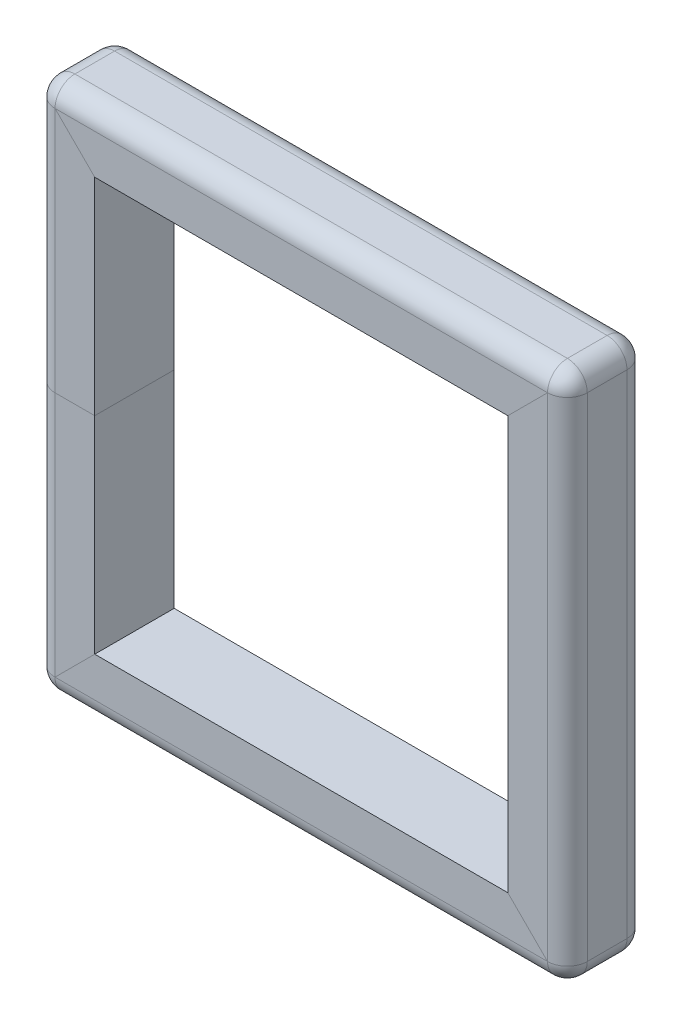
SolidWorks part; units mm, degrees
ref_plane "Front Plane" through (0, 0, 0) normal (0, 0, 1) x (1, 0, 0)
ref_plane "Top Plane" through (0, 0, 0) normal (0, 1, 0) x (1, 0, 0)
ref_plane "Right Plane" through (0, 0, 0) normal (1, 0, 0) x (0, 0, -1)
sketch "Sketch1" plane through (0, 0, 0) normal (0, 1, 0) x (1, 0, 0)
  line L0 (-63.5, 127) -> (-63.5, 0) construction
  line L1 (0, 0) -> (-63.5, 0)
  line L2 (0, 0) -> (0, 127)
  line L3 (0, 127) -> (-63.5, 127)
  line L5 (-95.25, 95.25) -> (-95.25, 31.75)
  arc A1 (-63.5, 127) -> (-95.25, 95.25) centre (-63.5, 95.25) ccw
  arc A2 (-95.25, 31.75) -> (-63.5, 0) centre (-63.5, 31.75) ccw
  dimension "D3" = 63.5
  dimension "D1" = 63.5
  dimension "D2" = 127
sketch "Sketch3" plane through (0, 0, 0) normal (0, 0, 1) x (1, 0, 0)
  line L1 (0, 330.2) -> (660.4, 330.2)
  line L2 (0, 330.2) -> (0, -330.2)
  line L3 (0, -330.2) -> (660.4, -330.2)
  line L4 (660.4, 330.2) -> (660.4, -330.2)
  dimension "D1" = 660.4
  dimension "D2" = 660.4
sweep "Sweep1" add profiles "Sketch1" path "Sketch3"
fillet "Fillet1" radius 31.75 12 edges at (-85.9506, -416.1506, -9.2994) (-85.9506, -416.1506, -117.7006) (746.3506, -416.1506, -9.2994) (746.3506, -416.1506, -117.7006) (746.3506, 416.1506, -9.2994) (746.3506, 416.1506, -117.7006) (-85.9506, 416.1506, -9.2994) (-85.9506, 416.1506, -117.7006) (-95.25, -425.45, -63.5) (755.65, -425.45, -63.5) (755.65, 425.45, -63.5) (-95.25, 425.45, -63.5)
